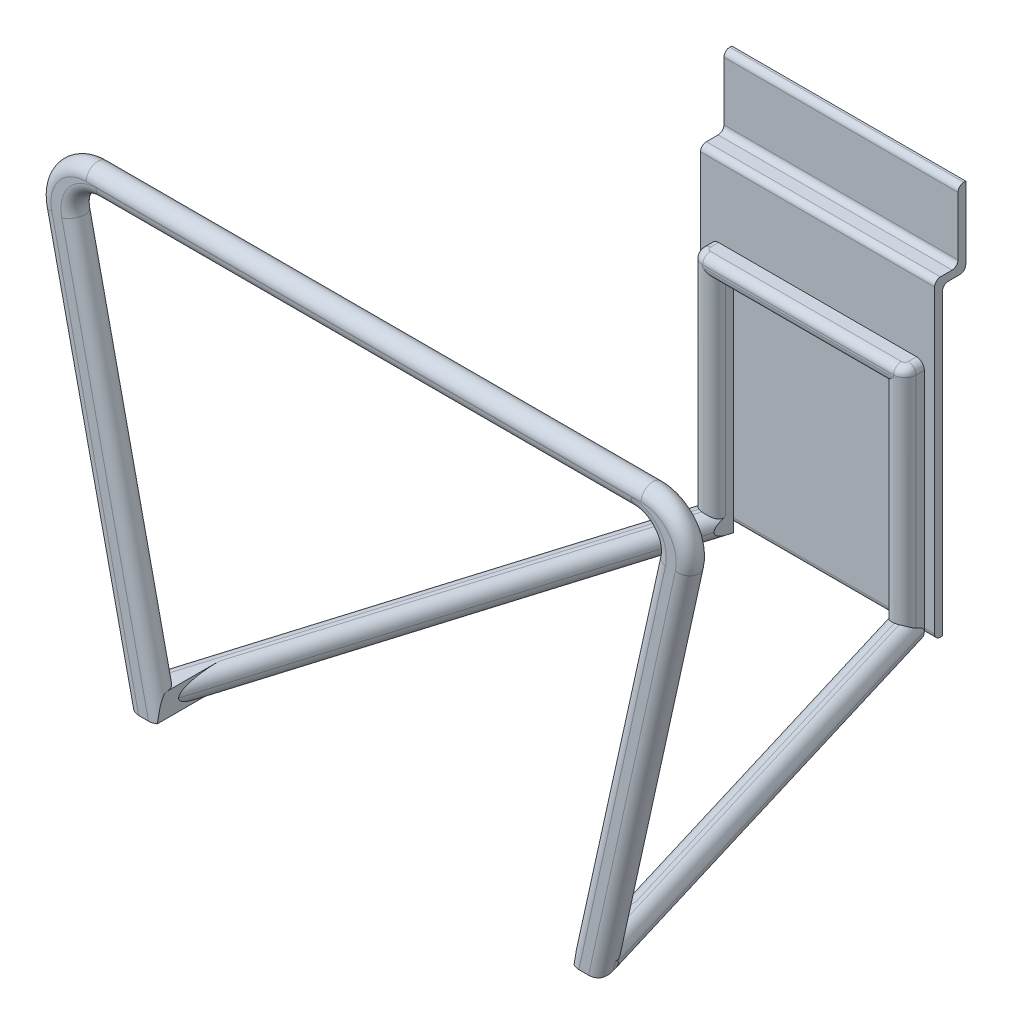
SolidWorks part; units mm, degrees
ref_plane "Front Plane" through (0, 0, 0) normal (0, 0, 1) x (1, 0, 0)
ref_plane "Top Plane" through (0, 0, 0) normal (0, 1, 0) x (1, 0, 0)
ref_plane "Right Plane" through (0, 0, 0) normal (1, 0, 0) x (0, 0, -1)
sketch "Sketch1" plane through (0, 0, 0) normal (0, 0, 1) x (1, 0, 0)
  line L1 (0, 0) -> (76.2, 0)
  line L2 (0, 0) -> (0, -101.6)
  line L3 (0, -101.6) -> (76.2, -101.6)
  line L4 (76.2, 0) -> (76.2, -101.6)
  dimension "D1" = 101.6
  dimension "D2" = 76.2
extrude "Boss-Extrude1" add sketch "Sketch1" along normal blind 2.54
sketch "Sketch3" plane through (0, 0, 0) normal (0, 0, -1) x (-1, 0, 0)
  line L0 (0, 0) -> (0, -101.6) construction
  line L1 (-76.2, 0) -> (0, 0)
  line L2 (-76.2, 0) -> (-76.2, -2.54)
  line L3 (-76.2, -2.54) -> (0, -2.54)
  line L4 (0, 0) -> (0, -2.54)
  dimension "D1" = 2.54
extrude "Boss-Extrude3" add sketch "Sketch3" along normal blind 7.62
sketch "Sketch4" plane through (0, 0, 0) normal (0, 1, 0) x (1, 0, 0)
  line L0 (76.2, -2.54) -> (76.2, 7.62) construction
  line L1 (0, 7.62) -> (76.2, 7.62)
  line L2 (0, 7.62) -> (0, 5.08)
  line L3 (0, 5.08) -> (76.2, 5.08)
  line L4 (76.2, 7.62) -> (76.2, 5.08)
  dimension "D1" = 2.54
extrude "Boss-Extrude4" add sketch "Sketch4" along normal blind 22.86
fillet "Fillet3" radius 1.905 6 edges at (38.1, -101.6, 2.54) (38.1, 0, 2.54) (38.1, 0, -5.08) (38.1, 22.86, -5.08) (38.1, -2.54, -7.62) (38.1, -2.54, 0)
sketch "Sketch5" plane through (0, 0, 2.54) normal (0, 0, 1) x (1, 0, 0)
  line L0 (3.3436, -104.5061) -> (3.3436, -24.5234)
  line L1 (3.3436, -24.5234) -> (72.8564, -24.5234)
  line L2 (72.8564, -24.5234) -> (72.8564, -104.5061)
  line L3 (72.8564, -104.5061) -> (65.476, -104.5061)
  line L4 (65.476, -104.5061) -> (65.476, -30.3591)
  line L5 (65.476, -30.3591) -> (10.724, -30.3591)
  line L6 (10.724, -30.3591) -> (10.724, -104.5061)
  line L7 (10.724, -104.5061) -> (3.3436, -104.5061)
  line L8 (38.1, -30.3591) -> (38.1, -99.695) construction
  line L9 (0, -99.695) -> (76.2, -99.695) construction
extrude "Boss-Extrude5" add sketch "Sketch5" along normal blind 6.35
sketch "Sketch14" plane through (0, -104.5061, 0) normal (0, -1, 0) x (1, 0, 0)
  line L0 (3.3436, 2.54) -> (-39.0394, 142.7099)
  line L1 (-29.739, 142.7099) -> (10.724, 8.89)
  line L2 (10.724, 8.89) -> (3.3436, 2.54)
  line L3 (-39.0394, 142.7099) -> (-29.739, 142.7099)
extrude "Boss-Extrude12" add sketch "Sketch14" against normal blind 7.62
sketch "Sketch15" plane through (0, 0, 142.7099) normal (0, 0, 1) x (1, 0, 0)
  line L0 (-39.0394, -104.5061) -> (-71.218, 41.3077)
  line L1 (-71.218, 41.3077) -> (-60.236, 41.3077)
  line L2 (-60.236, 41.3077) -> (-29.739, -96.8861)
  line L4 (-39.0394, -104.5061) -> (-29.739, -104.5061)
  line L5 (-29.739, -104.5061) -> (-29.739, -96.8861)
extrude "Boss-Extrude14" add sketch "Sketch15" along normal blind 7.62
ref_plane "Plane1" through (38.1, 0, 0) normal (-1, 0, 0) x (0, 0, 1)
ref_plane "Plane2" through (134.62, 0, 0) normal (1, 0, 0) x (0, 0, -1)
ref_plane "Plane3" through (-58.42, 0, 0) normal (1, 0, 0) x (0, 0, -1)
mirror "Mirror1" about plane through (38.1, 0, 0) normal (-1, 0, 0) of "Boss-Extrude14", "Boss-Extrude12"
sketch "Sketch17" plane through (105.939, 0, 0) normal (-1, 0, 0) x (0, 0, 1)
  line L0 (150.3299, 41.3077) -> (150.3299, -104.5061) construction
  line L1 (142.7099, 41.3077) -> (150.3299, 41.3077)
  line L2 (142.7099, 41.3077) -> (142.7099, 33.4476)
  line L3 (142.7099, 33.4476) -> (150.3299, 33.4476)
  line L4 (150.3299, 41.3077) -> (150.3299, 33.4476)
extrude "Boss-Extrude15" add sketch "Sketch17" along normal up to surface and the other way up to surface up to face at (-44.9875, -27.7892, 146.5199) other way up to face at (121.1875, -27.7892, 146.5199)
fillet "Fillet5" radius 7.62 2 edges at (134.7014, 33.4476, 146.5199) (-58.5014, 33.4476, 146.5199)
fillet "Fillet6" radius 15.24 2 edges at (147.418, 41.3077, 146.5199) (-71.218, 41.3077, 146.5199)
fillet "Fillet7" 2 edges at (38.1, 41.3077, 150.3299) (38.1, 41.3077, 142.7099) type full round first side face at (38.1, -25.5463, 150.3299) second side face at (38.1, -24.4577, 142.7099) middle face at (38.1, 41.3077, 146.5199)
fillet "Fillet8" 2 edges at (38.1, 33.4476, 150.3299) (38.1, 33.4476, 142.7099) type full round first side face at (38.1, -26.1006, 150.3299) second side face at (38.1, -11.7631, 142.7099) middle face at (38.1, 33.4476, 146.5199)
fillet "Fillet10" 2 edges at (3.3436, -60.7048, 8.89) (10.724, -63.6226, 8.89) type full round first side face at (3.3436, -60.7048, 5.715) second side face at (10.724, -77.7186, 5.715) middle face at (38.1, -62.1637, 8.89)
fillet "Fillet11" 2 edges at (72.8564, -60.7048, 8.89) (65.476, -63.6226, 8.89) type full round first side face at (72.8564, -60.7048, 5.715) second side face at (65.476, -77.7186, 5.715) middle face at (48.4554, -50.5895, 8.89)
fillet "Fillet12" radius 2.54 6 edges at (72.8564, -24.5234, 3.8699) (71.7756, -24.5234, 7.8092) (3.3436, -24.5234, 3.8699) (4.4244, -24.5234, 7.8092) (38.1, -30.3591, 8.89) (38.1, -24.5234, 8.89)
fillet "Fillet13" radius 3.81 8 edges at (94.0479, -104.5061, 72.6249) (85.7075, -104.5061, 75.7999) (85.7075, -96.8861, 75.7999) (94.1797, -96.8861, 73.0607) (-17.8479, -104.5061, 72.6249) (-9.5075, -104.5061, 75.7999) (-9.5075, -96.8861, 75.7999) (-17.9797, -96.8861, 73.0607)
